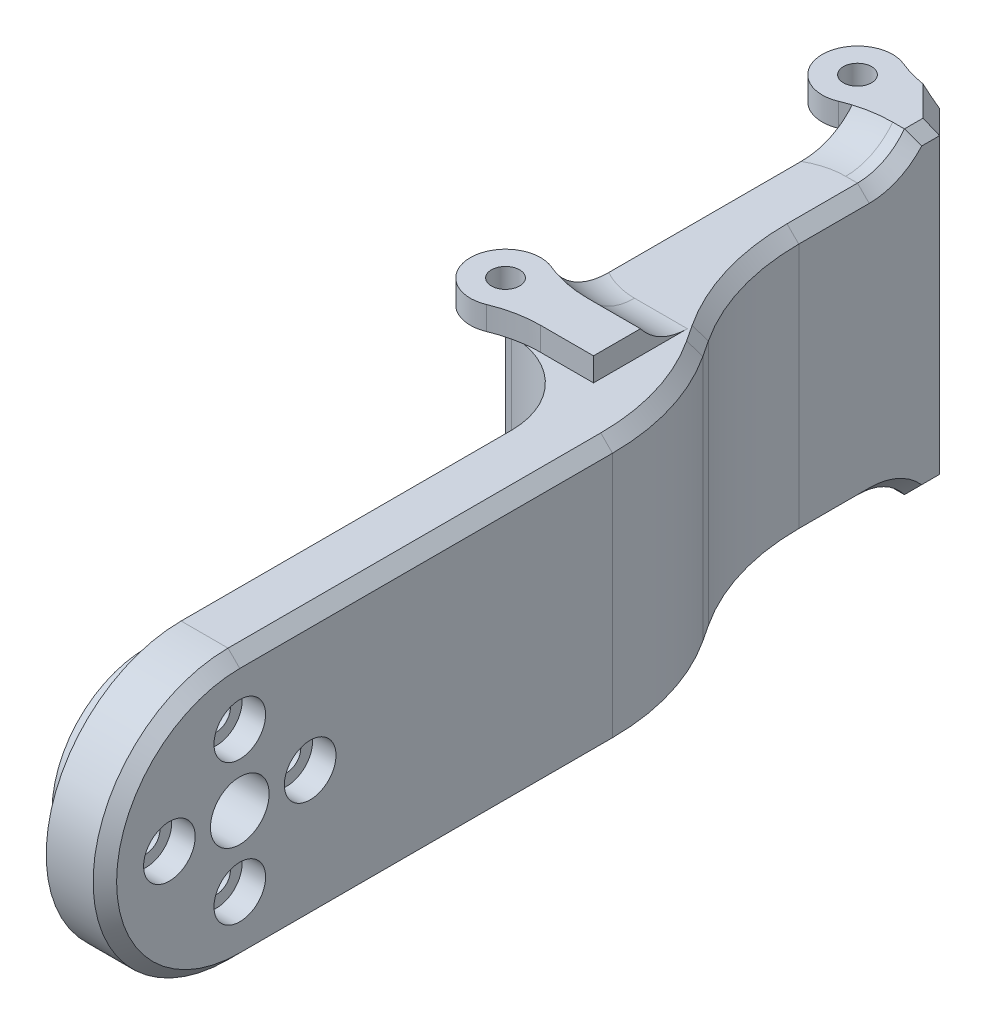
SolidWorks part; units mm, degrees
ref_plane "Front" through (0, 0, 0) normal (0, 0, 1) x (1, 0, 0)
ref_plane "Top" through (0, 0, 0) normal (0, 1, 0) x (1, 0, 0)
ref_plane "Right" through (0, 0, 0) normal (1, 0, 0) x (0, 0, -1)
sketch "Sketch1" plane through (0, 0, 0) normal (1, 0, 0) x (0, 0, -1)
  line L0 (0, 11.5) -> (35.1488, 11.5)
  line L1 (69.1488, 11.5) -> (69.1488, -11.5)
  line L4 (69.1488, 0) -> (0, 0) construction
  line L6 (35.1488, 11.5) -> (69.1488, 11.5)
  line L8 (0, -11.5) -> (35.1488, -11.5)
  line L9 (35.1488, -11.5) -> (69.1488, -11.5)
  line L10 (35.1488, 11.5) -> (35.1488, -11.5) construction
  line L11 (-24.3952, -10.253) -> (-27.9307, -13.7886) construction
  circle A0 centre (0, 0) radius 11.5
  circle A1 centre (0, 0) radius 31.1488 construction
  circle A2 centre (0, 0) radius 2.5
  circle A3 centre (0, 0) radius 13.7931 construction
  point P14 (31.1488, 0)
  line B0 (0, 0) -> (6.7175, 6.7175) construction
  line B1 (-24.3952, -10.253) -> (-0.3536, 13.7886) construction
  line B2 (-24.3952, -10.253) -> (-10.253, -24.3952) construction
  line B3 (-10.253, -24.3952) -> (13.7886, -0.3536) construction
  line B4 (-0.3536, 13.7886) -> (13.7886, -0.3536) construction
  line B5 (67.1488, 11.5) -> (67.1488, -11.5) construction
  line B6 (35.1488, 11.5) -> (69.1488, 11.5) construction
  line B7 (35.1488, 11.5) -> (35.1488, -11.5) construction
  line B8 (35.1488, -11.5) -> (69.1488, -11.5) construction
  line B9 (69.1488, 11.5) -> (69.1488, -11.5) construction
  line B10 (37.1488, 11.5) -> (37.1488, -11.5) construction
  dimension "D1" = 23
  dimension "D2" = 5
  dimension "D3" = 4
  dimension "D5" = 5
  dimension "D4" = 45
sketch_block_instance "430 Size Flat Block-1"
sketch_block "430 Size Flat Block" parameters "D1"=20, "D2"=34, "D3"=9.5
sketch_block_instance "DYNAMIXEL 330 Side-1"
sketch_block "DYNAMIXEL 330 Side" parameters "D1"=30, "D2"=34, "D3"=23, "D4"=2, "D5"=36.3112, "D6"=36.3112, "D7"=9.4648, "D8"=9.3216
extrude "Boss-Extrude1" add sketch "Sketch1" along normal blind 5 contours A0 A2 | A0 L8 L9 L1 L6 L0 | L6 | B7 L6 | L9 B10 | L9 region at (0, 0, -39.0357) region at (0, 7.9017, -7.9017)
sketch "Sketch7" plane through (0, 0, 0) normal (-1, 0, 0) x (0, 0, 1)
  circle A0 centre (0, 0) radius 8
  dimension "D1" = 16
extrude "Boss-Extrude4" add sketch "Sketch7" along normal blind 3
hole_wizard "CBORE for M2 SHCS1" positions "Sketch2" profile "Sketch3" counterbore size "M2" standard "ANSI Metric" end condition through all
sketch "Sketch2" plane through (5, 0, 0) normal (1, 0, 0) x (0, 0, -1)
  line L0 (0, 0) -> (0, 6) construction
  circle A0 centre (0, 0) radius 6
  point P5 (0, 6)
  point P12 (6, 0)
  point P13 (0, -6)
  point P14 (-6, 0)
  dimension "D1" = 12
  dimension "D2" = 4
sketch "Sketch3" plane through (5, 0, 6) normal (0, 1, 0) x (0, 0, -1)
  line L0 (0, 0) -> (0, 8)
  line L1 (0, 8) -> (1.2, 8)
  line L3 (1.2, 8) -> (1.2, 2)
  line L4 (1.2, 2) -> (2.2, 2)
  line L5 (2.2, 2) -> (2.2, 0)
  line L7 (2.2, 0) -> (0, 0)
  line L11 (0, -6.35) -> (0, 107.95) construction
  dimension "Thru Hole Dia." = 2.4
  dimension "Thru Hole Depth" = 8
  dimension "C'Bore Dia." = 4.4
  dimension "C'Bore Depth" = 2
sketch "Sketch4" plane through (0, 0, 0) normal (-1, 0, 0) x (0, 0, 1)
  line L0 (0, -11.5) -> (-69.1488, -11.5) construction
  line L1 (-69.1488, 11.5) -> (-35.1488, 11.5)
  line L2 (-69.1488, 11.5) -> (-69.1488, -11.5)
  line L3 (-69.1488, -11.5) -> (-35.1488, -11.5)
  line L4 (-35.1488, 11.5) -> (-35.1488, -11.5)
  dimension "D1" = 34
extrude "Boss-Extrude2" add sketch "Sketch4" along normal blind 7.5
sketch "Sketch5" plane through (0, 11.5, 0) normal (0, 1, 0) x (1, 0, 0)
  line L0 (-7.5, 35.1488) -> (-7.5, 69.1488) construction
  line L1 (5, 69.1488) -> (-7.5, 69.1488) construction
  line L2 (-9.5, 69.1488) -> (-7.5, 69.1488)
  line L3 (-9.5, 35.1488) -> (-7.5, 35.1488)
  line L4 (-7.5, 69.1488) -> (0, 69.1488)
  line L5 (-7.5, 35.1488) -> (0, 35.1488)
  line L6 (0, 35.1488) -> (0, 39.1488)
  line L7 (0, 39.1488) -> (-9.5, 39.1488)
  line L8 (0, 69.1488) -> (0, 65.1488)
  line L9 (0, 65.1488) -> (-9.5, 65.1488)
  arc A0 (-9.5, 39.1488) -> (-9.5, 35.1488) centre (-9.5, 37.1488) ccw
  arc A1 (-9.5, 69.1488) -> (-9.5, 65.1488) centre (-9.5, 67.1488) ccw
  circle A2 centre (-9.5, 37.1488) radius 1.2
  circle A3 centre (-9.5, 67.1488) radius 1.2
  line B0 (-27.5, 35.1488) -> (-7.5, 35.1488) construction
  line B1 (-7.5, 35.1488) -> (-7.5, 69.1488) construction
  line B2 (-7.5, 69.1488) -> (-27.5, 69.1488) construction
  line B3 (-27.5, 69.1488) -> (-27.5, 35.1488) construction
  dimension "D1" = 2.4
  dimension "D2" = 2.4
  dimension "D3" = 7.5
sketch_block_instance "DYNAMIXEL 330 Front-1"
sketch_block "DYNAMIXEL 330 Front" parameters "D1"=34, "D2"=20, "D3"=30, "D4"=16, "D5"=2, "D6"=2, "D7"=9.5, "D8"=10
extrude "Boss-Extrude3" add sketch "Sketch5" along normal blind 2 contours L6 L7 | L7 A0 L3 | L9 L8 | L2 A1 L9 region at (-5.0943, 11.5, -67.1488) region at (-5.0943, 11.5, -37.1488)
mirror "Mirror1" about plane through (0, 0, 0) normal (0, 1, 0) of "Boss-Extrude3"
sketch "Sketch6" plane through (0, 11.5, 0) normal (0, 1, 0) x (1, 0, 0)
  line L0 (-2.5, 69.1488) -> (-2.5, 49.1488)
  line L1 (-2.5, 49.1488) -> (5, 37.7624)
  line L3 (-2.5, 69.1488) -> (5, 69.1488)
  line L4 (5, 69.1488) -> (5, 37.7624)
  line L5 (0, 39.1488) -> (-9.5, 39.1488) construction
  line L6 (-7.5, 39.1488) -> (-7.5, 65.1488) construction
  line L7 (5, 0) -> (5, 69.1488) construction
  dimension "D1" = 10
  dimension "D2" = 5
extrude "Cut-Extrude1" cut sketch "Sketch6" against normal through all and the other way through all
sketch "Sketch8" plane through (0, 13.5, 0) normal (0, 1, 0) x (1, 0, 0)
  circle A0 centre (-9.5, 67.1488) radius 3
  circle A1 centre (-9.5, 67.1488) radius 1.2 construction
  circle A2 centre (-9.5, 67.1488) radius 1.2
  circle A3 centre (-9.5, 37.1488) radius 3
  circle A4 centre (-9.5, 37.1488) radius 1.2 construction
  circle A5 centre (-9.5, 37.1488) radius 1.2
  dimension "D1" = 6
extrude "Boss-Extrude5" add sketch "Sketch8" against normal blind 2
mirror "Mirror2" about plane through (0, 0, 0) normal (0, 1, 0) of "Boss-Extrude5"
fillet "Fillet4" radius 10 4 edges at (-7.2639, 12.5, -69.1488) (-7.2639, 12.5, -35.1488) (-7.2639, 12.5, -39.1488) (-7.2639, 12.5, -65.1488)
fillet "Fillet2" radius 20 2 edges at (-2.5, 0, -49.1488) (5, 0, -37.7624)
fillet "Fillet3" radius 5 6 edges at (-3.5, 11.5, -65.1488) (-2.25, 11.5, -39.1488) (-3.632, -11.5, -39.1488) (-4.882, -11.5, -65.1488) (-6.0176, 11.5, -65.033) (-6.0176, 11.5, -39.2647)
fillet "Fillet5" radius 7 1 edges at (0, 0, -35.1488)
chamfer "Chamfer4" distance 2 angle 45 1 edges at (-2.5, 0, -69.1488)
chamfer "Chamfer1" distance 1 angle 45 17 edges at (-1.6579, -11.5, -49.4013) (1.25, -11.5, -43.4556) (4.1579, -11.5, -37.5099) (-1.6579, 11.5, -49.4013) (5, -11.5, -15.8837) (1.25, 11.5, -43.4556) (5, 0, 11.5) (4.1579, 11.5, -37.5099) (5, 11.5, -15.8837) (-2.5, -12.0279, -63.3849) (-2.5, -11.5, -58.1463) (-2.5, 12.0279, -63.3849) (-2.5, 11.5, -58.1463) (-2.5, -13.5, -66.1488) (-3.5, -13.5, -68.1488) (-2.5, 13.5, -66.1488) (-3.5, 13.5, -68.1488)
